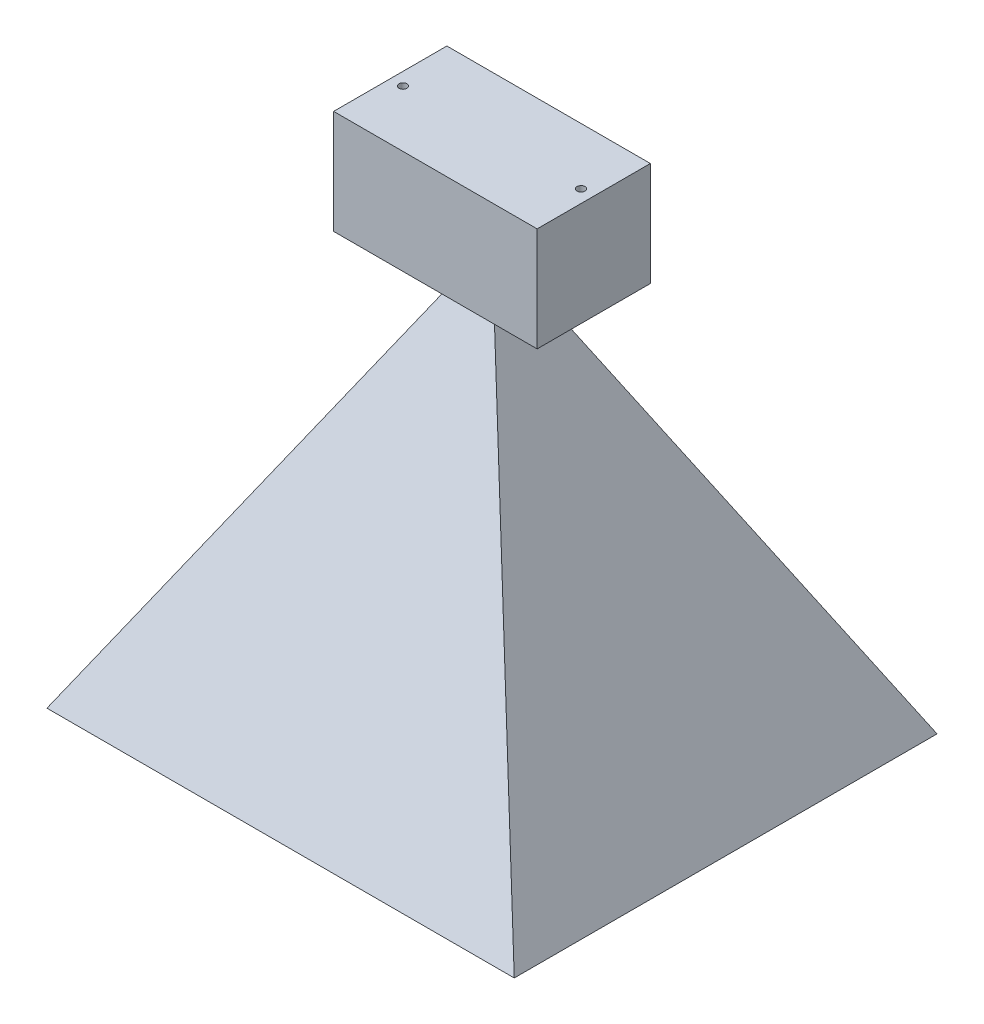
SolidWorks part; units mm, degrees
ref_plane "Front Plane" through (0, 0, 0) normal (0, 0, 1) x (1, 0, 0)
ref_plane "Top Plane" through (0, 0, 0) normal (0, 1, 0) x (1, 0, 0)
ref_plane "Right Plane" through (0, 0, 0) normal (1, 0, 0) x (0, 0, -1)
ref_plane "distance of measurement" through (0, 114.3, 0) normal (0, 1, 0) x (1, 0, 0)
sketch "Sketch1" plane through (0, 0, 0) normal (0, 1, 0) x (1, 0, 0)
  line L1 (-66.675, -60.325) -> (66.675, -60.325)
  line L2 (-66.675, -60.325) -> (-66.675, 60.325)
  line L3 (-66.675, 60.325) -> (66.675, 60.325)
  line L4 (66.675, -60.325) -> (66.675, 60.325)
  line L5 (-66.675, -60.325) -> (66.675, 60.325) construction
  line L6 (-66.675, 60.325) -> (66.675, -60.325) construction
  point P0 (0, 0)
  dimension "D1" = 133.35
  dimension "D2" = 120.65
sketch "Sketch2" plane through (0, 114.3, 0) normal (0, 1, 0) x (1, 0, 0)
  line L0 (-66.675, -60.325) -> (66.675, 60.325) construction
  line L1 (-2.3859, -2.1587) -> (2.3859, -2.1587)
  line L2 (-2.3859, -2.1587) -> (-2.3859, 2.1587)
  line L3 (-2.3859, 2.1587) -> (2.3859, 2.1587)
  line L4 (2.3859, -2.1587) -> (2.3859, 2.1587)
  line L5 (-2.3859, -2.1587) -> (2.3859, 2.1587) construction
  line L6 (-2.3859, 2.1587) -> (2.3859, -2.1587) construction
  point P0 (0, 0)
loft "FOV" add profiles "Sketch2", "Sketch1" connector at (-2.3859, 114.3, 2.1587) connector at (-66.675, 0, 60.325)
sketch "Sketch3" plane through (0, 114.3, 0) normal (0, 1, 0) x (1, 0, 0)
  circle A0 centre (0, 0) radius 8.509
  dimension "D1" = 17.018
extrude "camera lens" add sketch "Sketch3" along normal blind 0.254
sketch "Sketch4" plane through (0, 114.554, 0) normal (0, 1, 0) x (1, 0, 0)
  line L1 (29.0322, -16.1544) -> (-29.0322, -16.1544)
  line L2 (29.0322, -16.1544) -> (29.0322, 16.1544)
  line L3 (29.0322, 16.1544) -> (-29.0322, 16.1544)
  line L4 (-29.0322, -16.1544) -> (-29.0322, 16.1544)
  line L5 (29.0322, -16.1544) -> (-29.0322, 16.1544) construction
  line L6 (29.0322, 16.1544) -> (-29.0322, -16.1544) construction
  point P0 (0, 0)
  dimension "D1" = 58.0644
  dimension "D2" = 32.3088
extrude "camera holder" add sketch "Sketch4" along normal blind 29.6672
ref_point "centre of vision"
ref_point "direction reference"
sketch "reference points sketch" plane through (0, 0, 0) normal (0, -1, 0) x (1, 0, 0)
  line L0 (-66.675, 60.325) -> (66.675, 60.325) construction
  line L1 (66.675, 60.325) -> (66.675, -60.325) construction
  line L2 (66.675, -60.325) -> (-66.675, -60.325) construction
  line L3 (-66.675, -60.325) -> (-66.675, 60.325) construction
  line L4 (-66.675, 60.325) -> (66.675, -60.325) construction
  line L5 (-66.675, -60.325) -> (66.675, 60.325) construction
  point P0 (0, 60.325)
  point P1 (66.675, 0)
  point P4 (0, -60.325)
  point P7 (-66.675, 0)
  point P10 (-37.641, -5.8964)
  point P13 (38.0085, -2.6387)
  point P14 (-5.9243, 56.4894)
  point P15 (-4.0089, -31.4959)
  point P16 (38.0085, -34.3887)
  point P17 (32.1757, 29.1113)
  point P20 (-28.575, 25.8536)
  point P23 (-41.6092, -37.6464)
  point P24 (-66.675, 60.325)
  point P26 (66.675, 60.325)
  point P28 (66.675, -60.325)
  point P30 (-66.675, -60.325)
  dimension "D1" = 31.75
  dimension "D2" = 0
  dimension "D3" = 38.1
  dimension "D4" = 31.75
  dimension "D5" = 31.75
  dimension "D6" = 38.1
  dimension "D7" = 38.1
  dimension "D8" = 31.75
  dimension "D9" = 38.1
  dimension "D10" = 31.75
  dimension "D11" = 38.1
  dimension "D12" = 38.1
ref_point "direction reference 0"
ref_point "direction reference 1"
ref_point "direction reference 2"
ref_point "direction reference 3"
ref_point "direction reference 4"
ref_point "direction reference 5"
ref_point "direction reference 6"
ref_point "direction reference 7"
ref_point "direction reference 8"
ref_point "direction reference 9"
ref_point "direction reference 10"
ref_point "direction reference 11"
ref_point "direction reference 12"
ref_point "direction reference 13"
ref_point "direction reference 14"
ref_point "direction reference 15"
hole_wizard "#4-40 Tapped Hole1" positions "Sketch6" profile "Sketch5" tap size "#4-40" standard "ANSI Inch" end condition up to next
sketch "Sketch6" plane through (0, 144.2212, 0) normal (0, 1, 0) x (1, 0, 0)
  point P0 (-25.4, 0)
  point P2 (25.4, 0)
  dimension "D1" = 25.4
  dimension "D2" = 25.4
sketch "Sketch5" plane through (-25.4, 144.2212, 0) normal (1, 0, 0) x (0, 0, 1)
  line L0 (0, 0) -> (0, 29.6672)
  line L1 (0, 29.6672) -> (1.1303, 29.6672)
  line L2 (1.1303, 29.6672) -> (1.1303, 0)
  line L5 (1.1303, 0) -> (0, 0)
  line L11 (0, -6.35) -> (0, 107.95) construction
  dimension "Thru Tap Drill Dia." = 2.2606
  dimension "Thru Tap Drill Depth" = 29.6672
cosmetic thread "Hole Thread1" parameters "D2"=2.8448
cosmetic thread "Hole Thread2" parameters "D2"=2.8448
ref_point "z-basis"
ref_point "y-basis"
